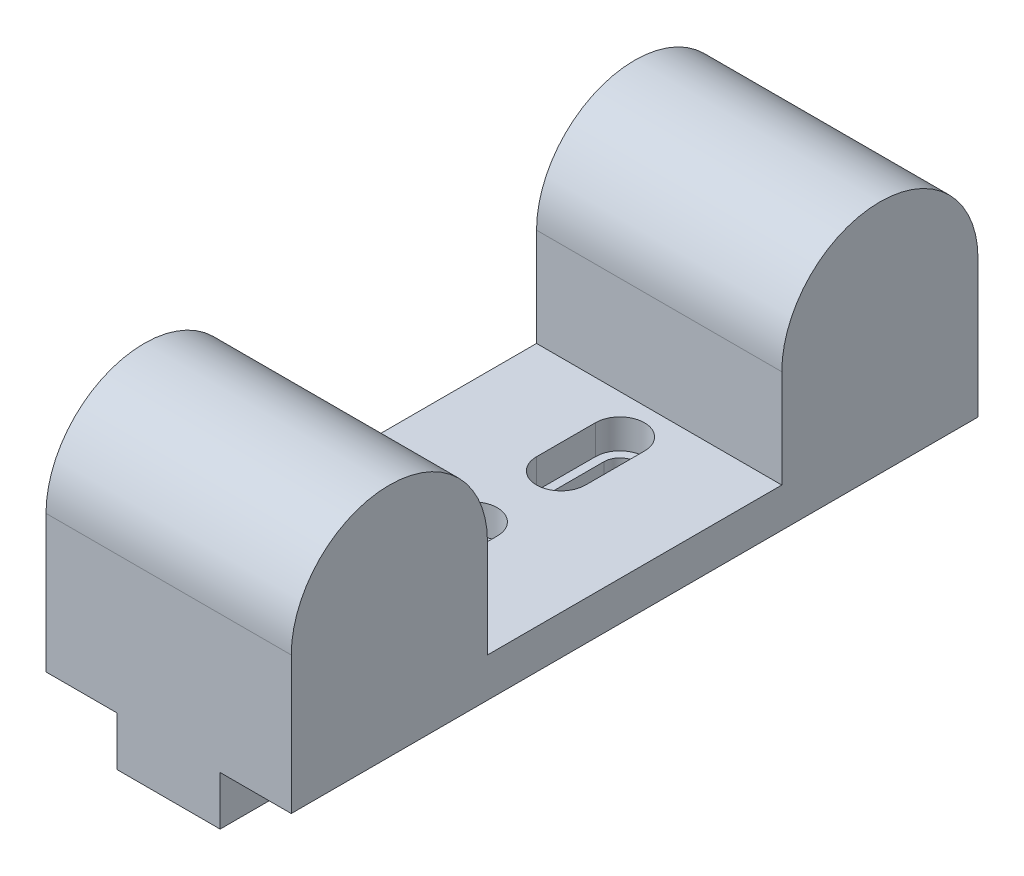
SolidWorks part; units mm, degrees
material "Alloy Steel"
ref_plane "Front Plane" through (0, 0, 0) normal (0, 0, 1) x (1, 0, 0)
ref_plane "Top Plane" through (0, 0, 0) normal (0, 1, 0) x (1, 0, 0)
ref_plane "Right Plane" through (0, 0, 0) normal (1, 0, 0) x (0, 0, -1)
sketch "Sketch1" plane through (0, 0, 0) normal (1, 0, 0) x (0, 0, -1)
  line L0 (10, 24) -> (60, 24) construction
  line L1 (0, 0) -> (70, 0)
  line L2 (0, 0) -> (0, 4)
  line L3 (0, 4) -> (70, 4)
  line L4 (70, 0) -> (70, 4)
  line L5 (91.0428, 39) -> (-12.4001, 39) construction
  line L6 (0, 4) -> (0, 14)
  line L7 (20, 14) -> (20, 4)
  line L9 (50, 14) -> (50, 4)
  line L11 (70, 14) -> (70, 4)
  arc A0 (0, 14) -> (20, 14) centre (10, 14) cw
  arc A3 (50, 14) -> (70, 14) centre (60, 14) cw
  point P6 (0, 0)
  point P7 (0, 0)
  point P19 (0, 0)
  point P20 (0, 0)
  point P21 (55.776, 11.1774)
  point P22 (70.0238, 5)
  point P23 (68.0839, 20)
  point P24 (10, 24)
  point P25 (62.888, 18.2894)
  point P26 (24.5321, 10.2595)
  point P27 (50, 8.9132)
  point P28 (68.5715, 20)
  point P29 (-12.4001, 40)
  point P30 (91.0428, 40)
  dimension "D1" = 4
  dimension "D2" = 15
  dimension "D3" = 20
  dimension "D4" = 50
  dimension "D5" = 70
  dimension "D6" = 39
extrude "Boss-Extrude1" add sketch "Sketch1" along normal mid plane 25 contours A0 L3 | L1 L4 L3 L2 | L3 region at (0, 2, -35) region at (0, 13.0665, -10) region at (0, 13.0665, -60)
sketch "Sketch2" plane through (0, 0, 0) normal (0, 1, 0) x (1, 0, 0)
  line L0 (12.5, 0) -> (-12.5, 0) construction
  line L1 (-5.25, 0) -> (5.25, 0)
  line L2 (-5.25, 0) -> (-5.25, 41.75)
  line L3 (-5.25, 41.75) -> (5.25, 41.75)
  line L4 (5.25, 0) -> (5.25, 41.75)
  arc A0 (-5.25, 41.75) -> (5.25, 41.75) centre (0, 41.75) cw
  point P8 (0, 0)
  point P9 (0, 0)
  dimension "D2" = 47
  dimension "D1" = 10.5
extrude "Boss-Extrude2" add sketch "Sketch2" against normal blind 5 contours A0 L3 | L1 L4 L3 L2 region at (0, 0, -20.875) region at (0, 0, -43.9782)
sketch "Sketch4" plane through (0, 0, 0) normal (0, 1, 0) x (1, 0, 0)
  line L0 (0, 0) -> (0, 46) construction
  line L1 (0, 46) -> (0, 40) construction
  line L2 (2.5, 46) -> (2.5, 40)
  line L3 (-2.5, 46) -> (-2.5, 40)
  line L4 (0, 31) -> (0, 25) construction
  line L5 (2.5, 31) -> (2.5, 25)
  line L6 (-2.5, 31) -> (-2.5, 25)
  line L7 (1.625, 46) -> (1.625, 40)
  line L8 (-1.625, 46) -> (-1.625, 40)
  line L9 (1.625, 31) -> (1.625, 25)
  line L10 (-1.625, 31) -> (-1.625, 25)
  arc A0 (2.5, 46) -> (-2.5, 46) centre (0, 46) ccw
  arc A1 (-2.5, 40) -> (2.5, 40) centre (0, 40) ccw
  arc A2 (2.5, 31) -> (-2.5, 31) centre (0, 31) ccw
  arc A3 (-2.5, 25) -> (2.5, 25) centre (0, 25) ccw
  arc A4 (-1.625, 40) -> (1.625, 40) centre (0, 40) ccw
  arc A5 (1.625, 46) -> (-1.625, 46) centre (0, 46) ccw
  arc A6 (-1.625, 25) -> (1.625, 25) centre (0, 25) ccw
  arc A7 (1.625, 31) -> (-1.625, 31) centre (0, 31) ccw
  point P3 (0, 43)
  point P9 (0, 28)
  dimension "D1" = 5
  dimension "D2" = 6
  dimension "D3" = 15
  dimension "D4" = 46
  dimension "D5" = 3.25
extrude "Cut-Extrude1" cut sketch "Sketch4" against normal through all both and the other way through all contours L9 A7 L10 A6 | L7 A5 L8 A4 region at (0, 0, -43) region at (0, 0, -28)
extrude "Cut-Extrude2" cut sketch "Sketch4<3>" against normal blind 3 from surface contours L6 A3 L5 A2 A7 L9 A6 L10 | L3 A1 L2 A0 A5 L7 A4 L8 region at (2.3792, 0, -43) region at (2.3792, 0, -28) starting at face at (0, 4, -35)
sketch "Sketch4<3>" plane through (0, 0, 0) normal (0, 1, 0) x (1, 0, 0) same geometry as "Sketch4"
